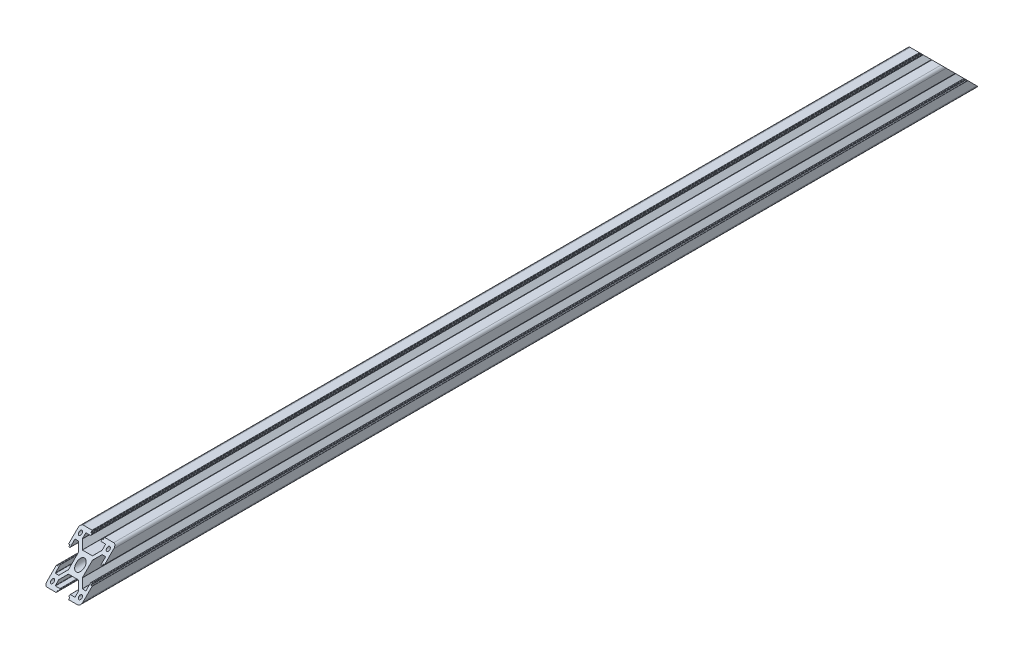
SolidWorks part; units mm, degrees
material "6063-T5"
ref_plane "Alzado" through (0, 0, 0) normal (0, 0, 1) x (1, 0, 0)
ref_plane "Planta" through (0, 0, 0) normal (0, 1, 0) x (1, 0, 0)
ref_plane "Vista lateral" through (0, 0, 0) normal (1, 0, 0) x (0, 0, -1)
sketch "Croquis1" plane through (0, 0, 0) normal (0, 0, 1) x (1, 0, 0)
  line L0 (0, 53.0989) -> (0, -48.4513) construction
  line L1 (-45.0818, 0) -> (46.476, 0) construction
  line L2 (-4.1615, 5.8) -> (4.1615, 5.8)
  line L3 (4.3029, 5.8586) -> (8.1914, 9.7471)
  line L4 (8.25, 9.8885) -> (8.25, 12.6)
  line L5 (8.05, 12.8) -> (4.3, 12.8)
  line L6 (4.1, 13) -> (4.1, 13.7)
  line L7 (4.3, 13.9) -> (4.9, 13.9)
  line L8 (5.1, 14.1) -> (5.1, 14.8)
  line L9 (5.3, 15) -> (12.8, 15)
  line L10 (0, 0) -> (45.9185, 45.9185) construction
  line L11 (15, 5.3) -> (15, 12.8)
  line L12 (13.9, 5.1) -> (14.8, 5.1)
  line L13 (13.9, 4.3) -> (13.9, 5.1)
  line L14 (13, 4.1) -> (13.7, 4.1)
  line L15 (12.8, 8.05) -> (12.8, 4.3)
  line L16 (9.8885, 8.25) -> (12.6, 8.25)
  line L17 (5.8586, 4.3029) -> (9.7471, 8.1914)
  line L18 (5.8, -4.1615) -> (5.8, 4.1615)
  line L19 (5.8586, -4.3029) -> (9.7471, -8.1914)
  line L20 (9.8885, -8.25) -> (12.6, -8.25)
  line L21 (12.8, -8.05) -> (12.8, -4.3)
  line L22 (13, -4.1) -> (13.7, -4.1)
  line L23 (13.9, -4.3) -> (13.9, -5.1)
  line L24 (13.9, -5.1) -> (14.8, -5.1)
  line L25 (15, -5.3) -> (15, -12.8)
  line L26 (5.3, -15) -> (12.8, -15)
  line L27 (5.1, -14.1) -> (5.1, -14.8)
  line L28 (4.3, -13.9) -> (4.9, -13.9)
  line L29 (4.1, -13) -> (4.1, -13.7)
  line L30 (8.05, -12.8) -> (4.3, -12.8)
  line L31 (8.25, -9.8885) -> (8.25, -12.6)
  line L32 (4.3029, -5.8586) -> (8.1914, -9.7471)
  line L33 (-4.1615, -5.8) -> (4.1615, -5.8)
  line L64 (-4.3029, -5.8586) -> (-8.1914, -9.7471)
  line L65 (-8.25, -9.8885) -> (-8.25, -12.6)
  line L66 (-8.05, -12.8) -> (-4.3, -12.8)
  line L67 (-4.1, -13) -> (-4.1, -13.7)
  line L68 (-4.3, -13.9) -> (-4.9, -13.9)
  line L69 (-5.1, -14.1) -> (-5.1, -14.8)
  line L70 (-5.3, -15) -> (-12.8, -15)
  line L71 (-15, -5.3) -> (-15, -12.8)
  line L72 (-13.9, -5.1) -> (-14.8, -5.1)
  line L73 (-13.9, -4.3) -> (-13.9, -5.1)
  line L74 (-13, -4.1) -> (-13.7, -4.1)
  line L75 (-12.8, -8.05) -> (-12.8, -4.3)
  line L76 (-9.8885, -8.25) -> (-12.6, -8.25)
  line L77 (-5.8586, -4.3029) -> (-9.7471, -8.1914)
  line L78 (-5.8586, 4.3029) -> (-9.7471, 8.1914)
  line L79 (-9.8885, 8.25) -> (-12.6, 8.25)
  line L80 (-12.8, 8.05) -> (-12.8, 4.3)
  line L81 (-13, 4.1) -> (-13.7, 4.1)
  line L82 (-13.9, 4.3) -> (-13.9, 5.1)
  line L83 (-13.9, 5.1) -> (-14.8, 5.1)
  line L84 (-15, 5.3) -> (-15, 12.8)
  line L85 (-5.3, 15) -> (-12.8, 15)
  line L86 (-5.1, 14.1) -> (-5.1, 14.8)
  line L87 (-4.3, 13.9) -> (-4.9, 13.9)
  line L88 (-4.1, 13) -> (-4.1, 13.7)
  line L89 (-8.05, 12.8) -> (-4.3, 12.8)
  line L90 (-8.25, 9.8885) -> (-8.25, 12.6)
  line L91 (-4.3029, 5.8586) -> (-8.1914, 9.7471)
  line L106 (-5.8, -4.1615) -> (-5.8, 4.1615)
  arc A0 (12.8, 15) -> (15, 12.8) centre (12.8, 12.8) cw
  arc A1 (5.1, 14.8) -> (5.3, 15) centre (5.3, 14.8) cw
  arc A2 (4.9, 13.9) -> (5.1, 14.1) centre (4.9, 14.1) ccw
  arc A3 (4.1, 13.7) -> (4.3, 13.9) centre (4.3, 13.7) cw
  arc A4 (4.3, 12.8) -> (4.1, 13) centre (4.3, 13) cw
  arc A5 (8.25, 12.6) -> (8.05, 12.8) centre (8.05, 12.6) ccw
  arc A6 (4.1615, 5.8) -> (4.3029, 5.8586) centre (4.1615, 6) ccw
  arc A7 (8.1914, 9.7471) -> (8.25, 9.8885) centre (8.05, 9.8885) ccw
  arc A8 (13, 4.1) -> (12.8, 4.3) centre (13, 4.3) cw
  arc A9 (5.8586, 4.3029) -> (5.8, 4.1615) centre (6, 4.1615) ccw
  arc A10 (9.8885, 8.25) -> (9.7471, 8.1914) centre (9.8885, 8.05) ccw
  arc A11 (12.8, 8.05) -> (12.6, 8.25) centre (12.6, 8.05) ccw
  arc A12 (13.9, 4.3) -> (13.7, 4.1) centre (13.7, 4.3) cw
  arc A13 (15, 5.3) -> (14.8, 5.1) centre (14.8, 5.3) cw
  arc A16 (15, -5.3) -> (14.8, -5.1) centre (14.8, -5.3) ccw
  arc A17 (13.9, -4.3) -> (13.7, -4.1) centre (13.7, -4.3) ccw
  arc A18 (12.8, -8.05) -> (12.6, -8.25) centre (12.6, -8.05) cw
  arc A19 (9.8885, -8.25) -> (9.7471, -8.1914) centre (9.8885, -8.05) cw
  arc A20 (5.8586, -4.3029) -> (5.8, -4.1615) centre (6, -4.1615) cw
  arc A21 (13, -4.1) -> (12.8, -4.3) centre (13, -4.3) ccw
  arc A22 (8.1914, -9.7471) -> (8.25, -9.8885) centre (8.05, -9.8885) cw
  arc A23 (4.1615, -5.8) -> (4.3029, -5.8586) centre (4.1615, -6) cw
  arc A24 (8.25, -12.6) -> (8.05, -12.8) centre (8.05, -12.6) cw
  arc A25 (4.3, -12.8) -> (4.1, -13) centre (4.3, -13) ccw
  arc A26 (4.1, -13.7) -> (4.3, -13.9) centre (4.3, -13.7) ccw
  arc A27 (4.9, -13.9) -> (5.1, -14.1) centre (4.9, -14.1) cw
  arc A28 (5.1, -14.8) -> (5.3, -15) centre (5.3, -14.8) ccw
  arc A29 (12.8, -15) -> (15, -12.8) centre (12.8, -12.8) ccw
  circle A44 centre (11.625, 11.625) radius 1.25
  circle A45 centre (11.625, -11.625) radius 1.25
  arc A60 (-12.8, -15) -> (-15, -12.8) centre (-12.8, -12.8) cw
  arc A61 (-5.1, -14.8) -> (-5.3, -15) centre (-5.3, -14.8) cw
  arc A62 (-4.9, -13.9) -> (-5.1, -14.1) centre (-4.9, -14.1) ccw
  arc A63 (-4.1, -13.7) -> (-4.3, -13.9) centre (-4.3, -13.7) cw
  arc A64 (-4.3, -12.8) -> (-4.1, -13) centre (-4.3, -13) cw
  arc A65 (-8.25, -12.6) -> (-8.05, -12.8) centre (-8.05, -12.6) ccw
  arc A66 (-4.1615, -5.8) -> (-4.3029, -5.8586) centre (-4.1615, -6) ccw
  arc A67 (-8.1914, -9.7471) -> (-8.25, -9.8885) centre (-8.05, -9.8885) ccw
  arc A68 (-13, -4.1) -> (-12.8, -4.3) centre (-13, -4.3) cw
  arc A69 (-5.8586, -4.3029) -> (-5.8, -4.1615) centre (-6, -4.1615) ccw
  arc A70 (-9.8885, -8.25) -> (-9.7471, -8.1914) centre (-9.8885, -8.05) ccw
  arc A71 (-12.8, -8.05) -> (-12.6, -8.25) centre (-12.6, -8.05) ccw
  arc A72 (-13.9, -4.3) -> (-13.7, -4.1) centre (-13.7, -4.3) cw
  arc A73 (-15, -5.3) -> (-14.8, -5.1) centre (-14.8, -5.3) cw
  arc A76 (-15, 5.3) -> (-14.8, 5.1) centre (-14.8, 5.3) ccw
  arc A77 (-13.9, 4.3) -> (-13.7, 4.1) centre (-13.7, 4.3) ccw
  arc A78 (-12.8, 8.05) -> (-12.6, 8.25) centre (-12.6, 8.05) cw
  arc A79 (-9.8885, 8.25) -> (-9.7471, 8.1914) centre (-9.8885, 8.05) cw
  arc A80 (-5.8586, 4.3029) -> (-5.8, 4.1615) centre (-6, 4.1615) cw
  arc A81 (-13, 4.1) -> (-12.8, 4.3) centre (-13, 4.3) ccw
  arc A82 (-8.1914, 9.7471) -> (-8.25, 9.8885) centre (-8.05, 9.8885) cw
  arc A83 (-4.1615, 5.8) -> (-4.3029, 5.8586) centre (-4.1615, 6) cw
  arc A84 (-8.25, 12.6) -> (-8.05, 12.8) centre (-8.05, 12.6) cw
  arc A85 (-4.3, 12.8) -> (-4.1, 13) centre (-4.3, 13) ccw
  arc A86 (-4.1, 13.7) -> (-4.3, 13.9) centre (-4.3, 13.7) ccw
  arc A87 (-4.9, 13.9) -> (-5.1, 14.1) centre (-4.9, 14.1) cw
  arc A88 (-5.1, 14.8) -> (-5.3, 15) centre (-5.3, 14.8) ccw
  arc A89 (-12.8, 15) -> (-15, 12.8) centre (-12.8, 12.8) ccw
  circle A104 centre (-11.625, -11.625) radius 1.25
  circle A105 centre (-11.625, 11.625) radius 1.25
  circle A120 centre (0, 0) radius 3.4
  point P5 (-15, -15)
  point P26 (15, 15)
  point P29 (5.1, 15)
  point P32 (5.1, 13.9)
  point P35 (4.1, 13.9)
  point P38 (4.1, 12.8)
  point P41 (8.25, 12.8)
  point P44 (4.2444, 5.8)
  point P47 (8.25, 9.8056)
  point P50 (12.8, 4.1)
  point P53 (5.8, 4.2444)
  point P56 (9.8056, 8.25)
  point P59 (12.8, 8.25)
  point P62 (13.9, 4.1)
  point P65 (15, 5.1)
  point P112 (5.8, 0)
  point P113 (0, 5.8)
  point P114 (15, -5.1)
  point P115 (13.9, -4.1)
  point P116 (12.8, -8.25)
  point P117 (9.8056, -8.25)
  point P118 (5.8, -4.2444)
  point P119 (12.8, -4.1)
  point P120 (8.25, -9.8056)
  point P121 (4.2444, -5.8)
  point P122 (8.25, -12.8)
  point P123 (4.1, -12.8)
  point P124 (4.1, -13.9)
  point P125 (5.1, -13.9)
  point P126 (5.1, -15)
  point P127 (15, -15)
  point P222 (0, -5.8)
  point P223 (-5.1, -15)
  point P224 (-5.1, -13.9)
  point P225 (-4.1, -13.9)
  point P226 (-4.1, -12.8)
  point P227 (-8.25, -12.8)
  point P228 (-4.2444, -5.8)
  point P229 (-8.25, -9.8056)
  point P230 (-12.8, -4.1)
  point P231 (-5.8, -4.2444)
  point P232 (-9.8056, -8.25)
  point P233 (-12.8, -8.25)
  point P234 (-13.9, -4.1)
  point P235 (-15, -5.1)
  point P236 (-5.8, 0)
  point P237 (-15, 5.1)
  point P238 (-13.9, 4.1)
  point P239 (-12.8, 8.25)
  point P240 (-9.8056, 8.25)
  point P241 (-5.8, 4.2444)
  point P242 (-12.8, 4.1)
  point P243 (-8.25, 9.8056)
  point P244 (-4.2444, 5.8)
  point P245 (-8.25, 12.8)
  point P246 (-4.1, 12.8)
  point P247 (-4.1, 13.9)
  point P248 (-5.1, 13.9)
  point P249 (-5.1, 15)
  point P250 (-15, 15)
  dimension "D8" = 2.2
  dimension "D9" = 0.2
  dimension "D12" = 6.8
  dimension "D1" = 2.2
  dimension "D2" = 8.25
  dimension "D3" = 15
  dimension "D4" = 9.2
  dimension "D5" = 4.1
  dimension "D6" = 5.1
  dimension "D7" = 2.2
  dimension "D11" = 3.375
extrude "Saliente-Extruir1" add sketch "Croquis1" along normal blind 750
sketch "Sketch1" plane through (0, 0, 0) normal (1, 0, 0) x (0, 0, -1)
  line L0 (-750, -15) -> (-720, 15)
  line L1 (-750, 15) -> (0, 15) construction
  line L2 (-750, -15) -> (0, -15) construction
  line L3 (-720, 15) -> (-750, 15)
  line L4 (-750, 15) -> (-750, -15)
  line L5 (-375, 141.1023) -> (-375, -105.3974) construction
  line L6 (-750, -4.1615) -> (-750, 4.1615) construction
  line L7 (0, -4.1615) -> (0, 4.1615) construction
  line L8 (0, 15) -> (0, -15)
  line L9 (-30, 15) -> (0, 15)
  line L10 (0, -15) -> (-30, 15)
  dimension "D1" = 45
extrude "Cut-Extrude1" cut sketch "Sketch1" against normal through all both and the other way through all
